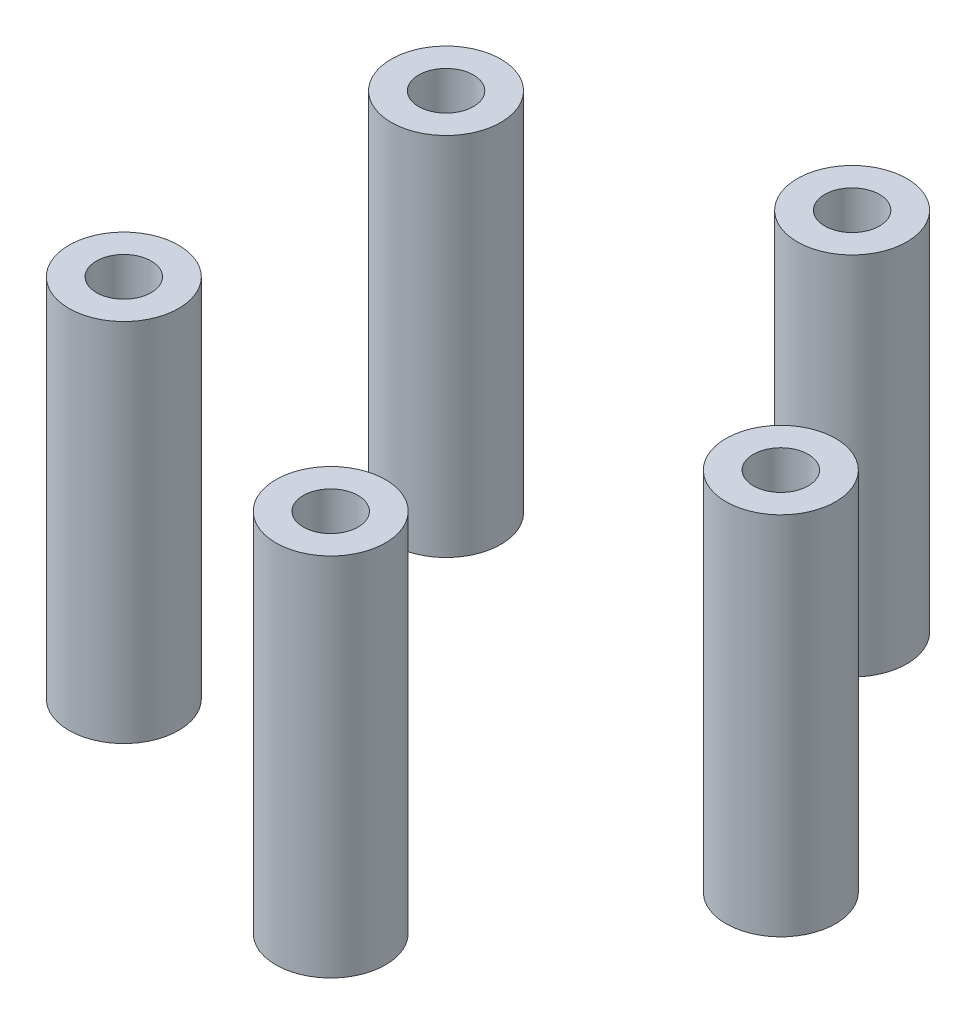
SolidWorks part; units mm, degrees
ref_plane "Front Plane" through (0, 0, 0) normal (0, 0, 1) x (1, 0, 0)
ref_plane "Top Plane" through (0, 0, 0) normal (0, 1, 0) x (1, 0, 0)
ref_plane "Right Plane" through (0, 0, 0) normal (1, 0, 0) x (0, 0, -1)
sketch "Sketch1" plane through (0, 0, 0) normal (0, 1, 0) x (1, 0, 0)
  line L0 (-15.8853, 8.8168) -> (-9.5853, 8.8168) construction
  line L1 (0.8853, 14.2658) -> (7.1853, 14.2658)
  line L2 (11.25, 0) -> (17.55, 0)
  line L3 (0.8853, -14.2658) -> (7.1853, -14.2658)
  line L4 (-15.8853, -8.8168) -> (-9.5853, -8.8168)
  circle A0 centre (-12.7353, 8.8168) radius 3
  circle A1 centre (-12.7353, 8.8168) radius 1.5
  circle A2 centre (4.6353, 14.2658) radius 3.75 construction
  circle A3 centre (3.4353, 14.2658) radius 3.75 construction
  circle A4 centre (15, 0) radius 3.75 construction
  circle A5 centre (13.8, 0) radius 3.75 construction
  circle A6 centre (4.6353, -14.2658) radius 3.75 construction
  circle A7 centre (3.4353, -14.2658) radius 3.75 construction
  circle A8 centre (-12.1353, -8.8168) radius 3.75 construction
  circle A9 centre (-13.3353, -8.8168) radius 3.75 construction
  circle A10 centre (-12.7353, -8.8168) radius 1.5
  circle A11 centre (-12.7353, -8.8168) radius 3
  circle A12 centre (4.0353, -14.2658) radius 1.5
  circle A13 centre (4.0353, -14.2658) radius 3
  circle A14 centre (14.4, 0) radius 1.5
  circle A15 centre (14.4, 0) radius 3
  circle A16 centre (4.0353, 14.2658) radius 1.5
  circle A17 centre (4.0353, 14.2658) radius 3
extrude "Boss-Extrude1" add sketch "Sketch1" along normal blind 12 and the other way blind 8 contours L4 A11 A10 | L4 A11 A10 | A0 A1 | L1 A17 A16 | L1 A17 A16 | L2 A15 A14 | L2 A15 A14 | L3 A13 A12 | L3 A13 A12 region at (4.0353, 0, -15.8329) region at (6.2853, 0, -14.1988) region at (14.4, 0, -1.5671) region at (16.65, 0, 0.0671) region at (4.0353, 0, 12.6988) region at (6.2853, 0, 14.3329) region at (-12.7353, 0, 7.2497) region at (-10.4853, 0, 8.8839) region at (-15.6504, 0, -8.8168)
